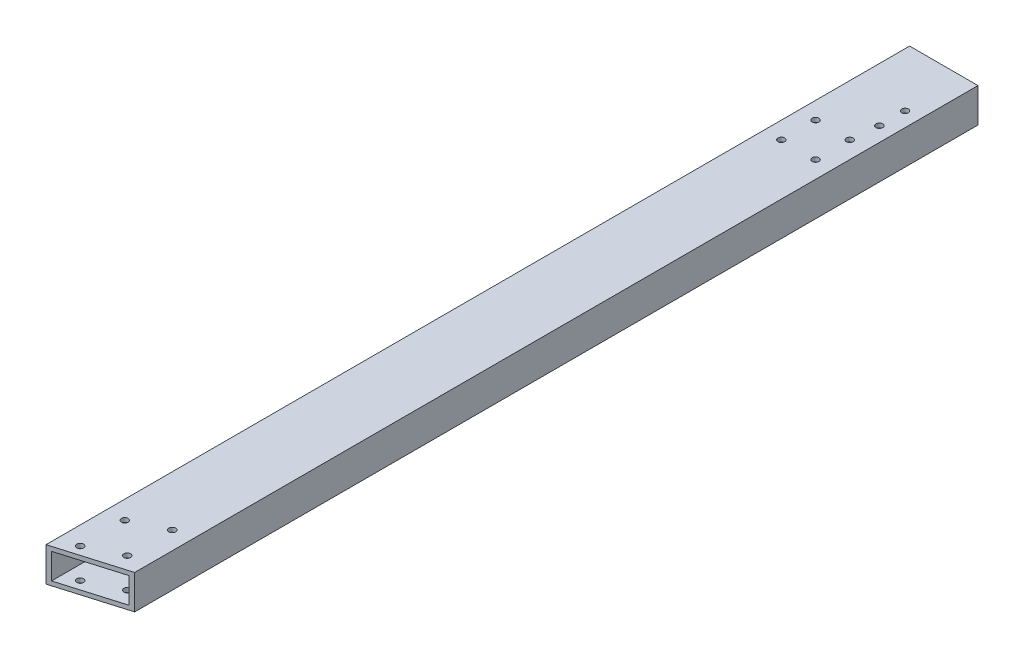
SolidWorks part; units mm, degrees
material "1060 Alloy"
ref_plane "Front Plane" through (0, 0, 0) normal (0, 0, 1) x (1, 0, 0)
ref_plane "Top Plane" through (0, 0, 0) normal (0, 1, 0) x (1, 0, 0)
ref_plane "Right Plane" through (0, 0, 0) normal (1, 0, 0) x (0, 0, -1)
sketch "Sketch1" plane through (0, 0, 0) normal (0, 0, 1) x (1, 0, 0)
  line L0 (-22.225, 9.525) -> (22.225, 9.525)
  line L2 (-25.4, 12.7) -> (25.4, 12.7)
  line L3 (-25.4, 12.7) -> (-25.4, -12.7)
  line L4 (-25.4, -12.7) -> (25.4, -12.7)
  line L5 (25.4, 12.7) -> (25.4, -12.7)
  line L10 (22.225, 9.525) -> (22.225, -9.525)
  line L11 (-22.225, -9.525) -> (22.225, -9.525)
  line L12 (-22.225, 9.525) -> (-22.225, -9.525)
  point P12 (0, 12.7)
  point P14 (25.4, 0)
  dimension "Wall Thickness" = 3.175
  dimension "Outside Width" = 50.8
  dimension "Outside Height" = 25.4
  dimension "Inside Height" = 19.05
  dimension "Inside Width" = 44.45
sketch "Sketch2" plane through (0, 0, 0) normal (1, 0, 0) x (0, 0, -1)
  line L0 (320.675, 0) -> (-320.675, 0)
  point P4 (0, 0)
  point P7 (-320.675, 0)
  point P10 (320.675, 0)
  dimension "Length" = 641.35
sketch "Sketch3" plane through (0, 0, 0) normal (0, 0, 1) x (1, 0, 0)
  line L21 (25.4, 12.7) -> (-25.4, 12.7)
  line L22 (25.4, -12.7) -> (25.4, 12.7)
  line L23 (-25.4, -12.7) -> (25.4, -12.7)
  line L24 (-25.4, 12.7) -> (-25.4, -12.7)
  line L25 (25.4, 12.7) -> (-25.4, 12.7)
  line L26 (25.4, -12.7) -> (25.4, 12.7)
  line L27 (-25.4, -12.7) -> (25.4, -12.7)
  line L28 (-25.4, 12.7) -> (-25.4, -12.7)
  line L29 (22.225, 9.525) -> (-22.225, 9.525)
  line L30 (22.225, -9.525) -> (22.225, 9.525)
  line L31 (-22.225, -9.525) -> (22.225, -9.525)
  line L32 (-22.225, 9.525) -> (-22.225, -9.525)
  line L33 (22.225, 9.525) -> (-22.225, 9.525)
  line L34 (22.225, -9.525) -> (22.225, 9.525)
  line L35 (-22.225, -9.525) -> (22.225, -9.525)
  line L36 (-22.225, 9.525) -> (-22.225, -9.525)
  dimension "D1" = 0
  dimension "D2" = 0
extrude "Boss-Extrude1" add sketch "Sketch3" along normal up to vertex (320.675 mm away) and the other way up to vertex (320.675 mm away) up to point (0, 0, 320.675) other way up to point (0, 0, -320.675)
sketch "Drawing Reference" plane through (0, 0, 0) normal (1, 0, 0) x (0, 0, -1)
  line L0 (-320.675, 0) -> (320.675, 0) construction
  line L1 (0, -12.7) -> (0, 12.7) construction
  line L2 (-320.675, -12.7) -> (320.675, -12.7) construction
  line L5 (-320.675, 12.7) -> (320.675, 12.7) construction
  point P7 (-284.099, 0)
  point P8 (284.099, 0)
  dimension "D1" = 36.576
sketch "Sketch4" plane through (0, 12.7, 0) normal (0, 1, 0) x (1, 0, 0)
  line L0 (-25.4, -320.675) -> (25.4, -305.6274)
  line L1 (25.4, -320.675) -> (25.4, 320.675) construction
  line L2 (25.4, -320.675) -> (-25.4, -320.675)
  dimension "D1" = 16.5
extrude "Cut-Extrude1" cut sketch "Sketch4" against normal through all and the other way through all flip side to cut
sketch "Sketch6" plane through (0, -12.7, 0) normal (0, -1, 0) x (1, 0, 0)
  line L0 (25.4, 305.6274) -> (22.1108, 294.5233) construction
  line L1 (25.4, 279.2824) -> (22.225, 279.2824) construction
  line L2 (25.4, 305.6274) -> (25.4, -320.675) construction
  line L3 (22.225, 279.2824) -> (22.225, 313.1512) construction
  line L4 (22.1108, 294.5233) -> (11.811, 297.5742) construction
  line L5 (-11.811, 250.3501) -> (-11.811, 328.3651) construction
  line L6 (-25.4, 320.675) -> (-27.5213, 313.5136) construction
  line L7 (-25.4, 287.6223) -> (-22.225, 287.6223) construction
  line L8 (-25.4, 320.675) -> (-25.4, -320.675) construction
  line L9 (-22.225, 287.6223) -> (-22.225, 328.3651) construction
  line L10 (-27.5213, 313.5136) -> (-11.811, 308.86) construction
  line L11 (11.811, 250.3501) -> (11.811, 313.1512) construction
  line L12 (-27.5213, 313.5136) -> (-36.5388, 283.071) construction
  line L13 (22.1108, 294.5233) -> (13.0933, 264.0807) construction
  line L14 (-37.6746, 250.3501) -> (48.6057, 250.3501) construction
  line L15 (-11.811, 287.6223) -> (-11.811, 328.3651) construction
  line L16 (11.811, 279.2824) -> (11.811, 313.1512) construction
  line L17 (-36.5388, 283.071) -> (-11.811, 275.7463) construction
  line L18 (13.0933, 264.0807) -> (11.811, 264.4606) construction
  line L19 (-11.811, 308.86) -> (11.811, 264.4606) construction
  line L20 (11.811, 297.5742) -> (-11.811, 275.7463) construction
  point P10 (0, 286.6603)
  dimension "D1" = 10.414
  dimension "D2" = 10.414
hole_wizard "#10 Clearance Hole1" positions "Sketch9" profile "Sketch10" hole size "#10" standard "ANSI Inch"
sketch "Sketch9" plane through (0, 12.7, 0) normal (0, 1, 0) x (1, 0, 0)
  line L0 (13.0933, -264.0807) -> (11.811, -264.4606) construction
  point P0 (-11.811, -275.7463)
  point P3 (-11.811, -308.86)
  point P6 (11.811, -297.5742)
  point P9 (12.0472, -264.3906)
sketch "Sketch10" plane through (-11.811, 12.7, 275.7463) normal (1, 0, 0) x (0, 0, 1)
  line L0 (0, 0) -> (0, 31.9757)
  line L1 (0, 31.9757) -> (2.4892, 30.48)
  line L2 (2.4892, 30.48) -> (2.4892, 0)
  line L5 (2.4892, 0) -> (0, 0)
  line L10 (0, 31.9757) -> (-2.4892, 30.48) construction
  line L11 (0, -6.35) -> (0, 107.95) construction
  dimension "Hole Dia." = 4.9784
  dimension "Hole Depth" = 30.48
  dimension "Drill Angle" = 118
sketch "Sketch12" plane through (0, -12.7, 0) normal (0, -1, 0) x (1, 0, 0)
  line L0 (13.0291, -316.23) -> (10.4891, -316.23) construction
  line L1 (-9.8309, -316.23) -> (-12.3709, -316.23) construction
  line L2 (13.0291, -299.72) -> (10.4891, -299.72) construction
  line L3 (-9.8309, -299.72) -> (-12.3709, -299.72) construction
hole_wizard "#10 Clearance Hole3" positions "Sketch15" profile "Sketch16" hole size "#10" standard "ANSI Inch"
sketch "Sketch15" plane through (0, -12.7, 0) normal (0, -1, 0) x (-1, 0, 0)
  point P0 (-13.0291, 299.72)
  point P3 (12.3709, 299.72)
  point P6 (12.3709, 316.23)
  point P9 (-13.0291, 316.23)
sketch "Sketch16" plane through (13.0291, -12.7, -299.72) normal (1, 0, 0) x (0, 0, -1)
  line L0 (0, 0) -> (0, 6.5757)
  line L1 (0, 6.5757) -> (2.4892, 5.08)
  line L2 (2.4892, 5.08) -> (2.4892, 0)
  line L5 (2.4892, 0) -> (0, 0)
  line L10 (0, 6.5757) -> (-2.4892, 5.08) construction
  line L11 (0, -6.35) -> (0, 107.95) construction
  dimension "Hole Dia." = 4.9784
  dimension "Hole Depth" = 5.08
  dimension "Drill Angle" = 118
sketch "Sketch17" plane through (0, -12.7, 0) normal (0, -1, 0) x (1, 0, 0)
  line L0 (12.7, -238.125) -> (-12.7, -238.125) construction
  line L1 (-12.7, -238.125) -> (-12.7, -212.725) construction
  line L2 (-12.7, -212.725) -> (12.7, -212.725) construction
  line L3 (12.7, -212.725) -> (12.7, -238.125) construction
hole_wizard "#10 Clearance Hole4" positions "Sketch18" profile "Sketch19" hole size "#10" standard "ANSI Inch" end condition through all
sketch "Sketch18" plane through (0, -12.7, 0) normal (0, -1, 0) x (-1, 0, 0)
  point P0 (-12.7, 238.125)
  point P3 (12.7, 238.125)
  point P6 (12.7, 212.725)
  point P14 (-12.7, 212.725)
  point P18 (-14.6226, 277.2519)
  point P21 (-14.6226, 258.2019)
sketch "Sketch19" plane through (12.7, -12.7, -238.125) normal (1, 0, 0) x (0, 0, -1)
  line L0 (0, 0) -> (0, 25.4)
  line L1 (0, 25.4) -> (2.4892, 25.4)
  line L2 (2.4892, 25.4) -> (2.4892, 0)
  line L5 (2.4892, 0) -> (0, 0)
  line L11 (0, -6.35) -> (0, 107.95) construction
  dimension "Thru Hole Dia." = 4.9784
  dimension "Thru Hole Depth" = 25.4
equation "\"D1@Drawing Reference\"=\"Outside Width@Sketch1\" * 0.72"
